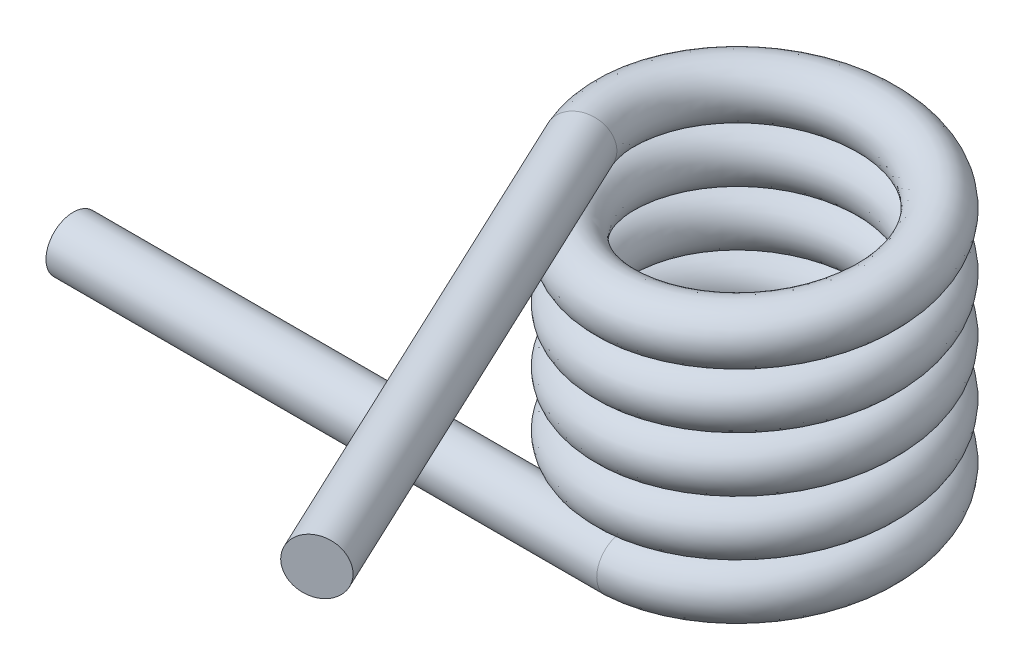
SolidWorks part; units mm, degrees
material "AISI 1020"
ref_plane "Спереди" through (0, 0, 0) normal (0, 0, 1) x (1, 0, 0)
ref_plane "Сверху" through (0, 0, 0) normal (0, 1, 0) x (1, 0, 0)
ref_plane "Справа" through (0, 0, 0) normal (1, 0, 0) x (0, 0, -1)
sketch "Эскиз1" plane through (0, 0, 0) normal (0, 1, 0) x (1, 0, 0)
  circle A0 centre (0, 0) radius 23 construction
  circle A1 centre (0, 0) radius 15 construction
  circle A2 centre (0, 0) radius 19
  dimension "D1" = 46
  dimension "D2" = 30
  dimension "D3" = 38
curve "Спираль1" pitch 8 height 38.56 radius 19 centre (0, 0, 0) axis (0, 1, 0) start towards (0, 0, 1)
ref_plane "Плоскость1" through (0, 0, 0) normal (-1, 0, 0) x (0, 0, 1)
sketch "Эскиз2" plane through (0, 0, 0) normal (-1, 0, 0) x (0, 0, 1)
  circle A0 centre (19, 0) radius 3.95
  dimension "D1" = 7.9
sweep "По траектории1" add profiles "Эскиз2" path "Спираль1"
extrude "Бобышка-Вытянуть1" add sketch "Эскиз2<2>" along normal blind 80
sketch "Эскиз2<2>" plane through (0, 0, 0) normal (-1, 0, 0) x (0, 0, 1) same geometry as "Эскиз2"
sketch "Эскиз4" plane through (0, 0, 0) normal (0.4258, 0, 0.9048) x (0.9048, 0, -0.4258)
  circle A0 centre (-19, 38.5599) radius 3.95 construction
  circle A1 centre (-19, 38.5599) radius 3.95
extrude "Бобышка-Вытянуть2" add sketch "Эскиз4" along normal blind 80
sketch "Эскиз5" plane through (0, 0, 0) normal (0, 1, 0) x (1, 0, 0)
  line L0 (0, -19) -> (-80, -19)
  line L1 (0, 10.45) -> (0, -10.45) construction
  line L2 (-18.9954, -0.4173) -> (-20.7526, 79.5634)
  line L3 (-80, -15.05) -> (-80, -22.95) construction
  circle A0 centre (0, 0) radius 19
  dimension "D1" = 115
equation "\"D3@Эскиз1\"=(\"D2@Эскиз1\"+\"D1@Эскиз1\")/2"
